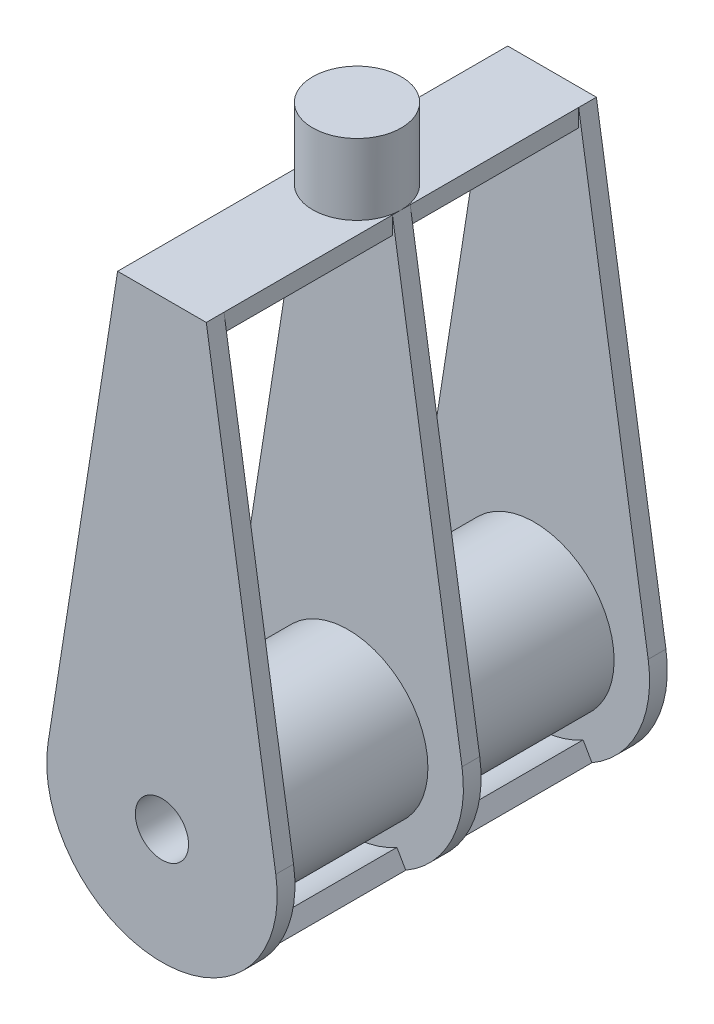
SolidWorks part; units mm, degrees
ref_plane "前视基准面" through (0, 0, 0) normal (0, 0, 1) x (1, 0, 0)
ref_plane "上视基准面" through (0, 0, 0) normal (0, 1, 0) x (1, 0, 0)
ref_plane "右视基准面" through (0, 0, 0) normal (1, 0, 0) x (0, 0, -1)
sketch "草图1" plane through (0, 0, 0) normal (0, 0, 1) x (1, 0, 0)
  line L0 (0, 0) -> (0, 26) construction
  line L1 (-2.5, 26) -> (-6.4214, 1.0076)
  line L2 (2.5, 26) -> (6.4214, 1.0076)
  line L3 (-2.5, 26) -> (2.5, 26)
  arc A1 (-6.4214, 1.0076) -> (6.4214, 1.0076) centre (0, 0) ccw
  circle A2 centre (0, 0) radius 1.5
  point P9 (0, 41.9332)
  dimension "D1" = 26
  dimension "D2" = 13
  dimension "D3" = 5
  dimension "D4" = 3
extrude "凸台-拉伸1" add sketch "草图1" along normal blind 1
sketch "草图2" plane through (0, 26, 0) normal (0, 1, 0) x (1, 0, 0)
  line L0 (2.5, -1) -> (2.5, 0) construction
  line L1 (-2.5, 0) -> (2.5, 0)
  line L2 (-2.5, 0) -> (-2.5, -22)
  line L3 (-2.5, -22) -> (2.5, -22)
  line L4 (2.5, 0) -> (2.5, -22)
  dimension "D1" = 22
extrude "凸台-拉伸2" add sketch "草图2" against normal blind 1
extrude "凸台-拉伸3" add sketch "草图1<2>" against normal blind 1 from surface starting at face at (0, 25.5, 22)
sketch "草图1<2>" plane through (0, 0, 0) normal (0, 0, 1) x (1, 0, 0) same geometry as "草图1"
ref_plane "基准面1" through (0, 0, 11) normal (0, 0, 1) x (1, 0, 0)
extrude "凸台-拉伸4" add sketch "草图1<3>" along normal mid plane 1 from surface starting at plane "基准面1"
sketch "草图1<3>" plane through (0, 0, 0) normal (0, 0, 1) x (1, 0, 0) same geometry as "草图1"
sketch "草图3" plane through (0, 26, 0) normal (0, 1, 0) x (1, 0, 0)
  line L0 (0, 0) -> (0, -22) construction
  line L1 (-2.5, -22) -> (2.5, -22) construction
  line L2 (2.5, -21) -> (2.5, -11.5) construction
  circle A0 centre (0, -11) radius 2.5
extrude "凸台-拉伸5" add sketch "草图3" along normal blind 4
sketch "草图4" plane through (0, 0, 0) normal (0, 0, -1) x (-1, 0, 0)
  line L0 (-2.75, -4.7631) -> (-3.25, -5.6292)
  line L1 (0, 0) -> (0, -10.8963) construction
  line L2 (2.75, -4.7631) -> (3.25, -5.6292)
  arc A0 (-6.4214, 1.0076) -> (6.4214, 1.0076) centre (0, 0) ccw construction
  arc A1 (-3.25, -5.6292) -> (3.25, -5.6292) centre (0, 0) ccw
  arc A2 (-2.75, -4.7631) -> (2.75, -4.7631) centre (0, 0) ccw
  arc A4 (-6.4214, 1.0076) -> (6.4214, 1.0076) centre (0, 0) ccw construction
  arc A5 (-5.4335, 0.8525) -> (5.4335, 0.8525) centre (0, 0) ccw construction
  dimension "D2" = 30
  dimension "D1" = 1
extrude "凸台-拉伸6" add sketch "草图4" against normal up to surface (22 mm away) up to face at (0, 11.6269, 22)
sketch "草图5" plane through (0, 0, 0) normal (0, 0, -1) x (-1, 0, 0)
  circle A0 centre (0, 0) radius 4.5
  circle A1 centre (0, 0) radius 1.5 construction
  circle A2 centre (0, 0) radius 1.5
  dimension "D1" = 9
extrude "凸台-拉伸7" add sketch "草图5" against normal up to surface (22 mm away) up to face at (0, 11.6269, 22)
ref_plane "基准面2" through (0, 0, 5.75) normal (0, 0, 1) x (1, 0, 0)
ref_plane "基准面3" through (0, 0, 16.25) normal (0, 0, 1) x (1, 0, 0)
sketch "草图6" plane through (0, 0, 5.75) normal (0, 0, 1) x (1, 0, 0)
  circle A0 centre (0, 0) radius 4.5 construction
  circle A1 centre (0, 0) radius 4.5
sketch "草图7" plane through (0, 0, 16.25) normal (0, 0, 1) x (1, 0, 0)
  circle A0 centre (0, 0) radius 4.5 construction
  circle A1 centre (0, 0) radius 4.5
